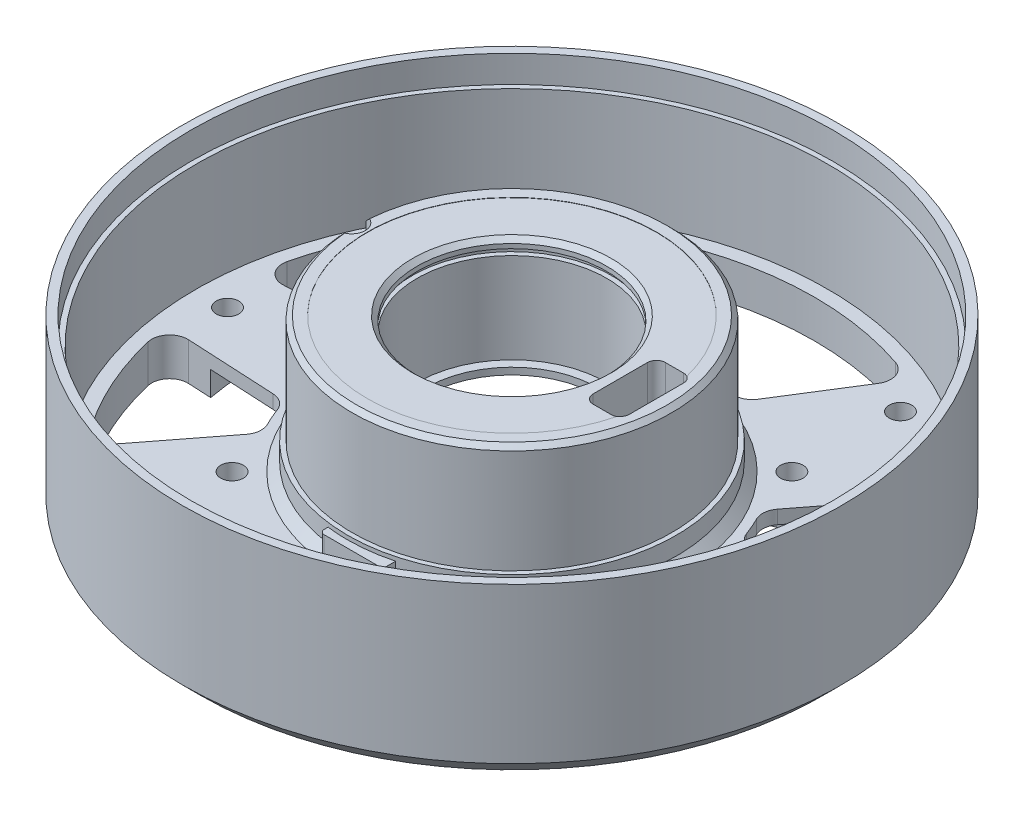
SolidWorks part; units mm, degrees
ref_plane "Front Plane" through (0, 0, 0) normal (0, 0, 1) x (1, 0, 0)
ref_plane "Top Plane" through (0, 0, 0) normal (0, 1, 0) x (1, 0, 0)
ref_plane "Right Plane" through (0, 0, 0) normal (1, 0, 0) x (0, 0, -1)
ref_axis "Axis1" through (0, 0, 0) along (0, 1, 0)
sketch "Sketch1" plane through (0, 0, 0) normal (0, 0, 1) x (1, 0, 0)
  line L0 (0, 0) -> (0, -50277.2651) construction
  line L1 (-17.7, 6) -> (-17.7, -6)
  line L2 (-17.7, -6) -> (-18.2, -6)
  line L3 (-18.2, -6) -> (-18.2, -8)
  line L4 (-19.2, -9) -> (-35, -9)
  line L7 (-35, -9) -> (-35, 3)
  line L8 (-35, 3) -> (-35.55, 3)
  line L9 (-35.55, 3) -> (-35.55, 6)
  line L10 (-35.55, 6) -> (-36.5, 6)
  line L11 (-36.5, 6) -> (-36.5, -11.2)
  line L12 (-34.5, -13.2) -> (-28.5, -13.2)
  line L13 (-28.5, -13.2) -> (-28.5, -10.5)
  line L14 (-28.5, -10.5) -> (-18.06, -10.5)
  line L23 (-16, 5.97) -> (-16, 6)
  line L24 (-16, 6) -> (-17.7, 6)
  line L25 (-19.25, -6) -> (19.25, -6) construction
  line L26 (19.25, 6) -> (-19.25, 6) construction
  line L27 (-34, 8) -> (-34, -6) construction
  line L31 (-16, 5.97) -> (-10.5, 5.97)
  line L32 (11.5, -13.2) -> (-11.5, -13.2) construction
  line L37 (-18.06, -10.5) -> (-14, -6.44)
  line L38 (-14, -6.44) -> (-9.5, -6.44)
  line L39 (-9.5, -6.44) -> (-9.5, -5.69)
  line L40 (-9.5, -5.69) -> (-10.5, -5.69)
  line L42 (-36.5, -11.2) -> (-34.5, -13.2)
  line L44 (-18.2, -8) -> (-19.2, -9)
  line L45 (-10.5, 5.97) -> (-10.5, 4.97)
  line L47 (-10.5, 4.97) -> (-11.03, 4.97)
  line L48 (-11.03, 4.97) -> (-11.03, 4.31)
  line L49 (-11.03, 4.31) -> (-10.5, 4.31)
  line L50 (-10.5, 4.31) -> (-10.5, -5.69)
  line L51 (8.9533, 4.31) -> (-8.9533, 4.31) construction
  line L52 (-8.9533, -5.69) -> (8.9533, -5.69) construction
  point P6 (-18.2, -9)
  point P15 (-36.5, -13.2)
  point P31 (-31.5, -13.2)
  dimension "D1" = 35.4
  dimension "D2" = 32
  dimension "D3" = 0.5
  dimension "D4" = 3
  dimension "D5" = 1
  dimension "D6" = 1.5
  dimension "D8" = 1.5
  dimension "D9" = 3
  dimension "D10" = 71.1
  dimension "D13" = 63
  dimension "D14" = 0.66
  dimension "D15" = 21
  dimension "D16" = 22.06
  dimension "D17" = 1
  dimension "D18" = 0.75
  dimension "D19" = 1
  dimension "D20" = 3.5
  dimension "D21" = 135
revolve "Revolve1" add sketch "Sketch1" angle 360 about L0
sketch "Sketch2" plane through (0, 0, 0) normal (0, 1, 0) x (1, 0, 0)
  circle A0 centre (-17.75, 0) radius 1.5
  dimension "D1" = 3
extrude "Cut-Extrude2" cut sketch "Sketch2" along normal up to next and the other way up to surface other way up to face at (0, -6, 18.2)
sketch "Sketch3" plane through (0, 0, 0) normal (0, 1, 0) x (1, 0, 0)
  circle A0 centre (-15.5, -15.5) radius 3.5
  circle A1 centre (15.5, -15.5) radius 3.5
  circle A2 centre (15.5, 15.5) radius 3.5
  circle A3 centre (-15.5, 15.5) radius 3.5
  dimension "D1" = 7
extrude "Boss-Extrude1" add sketch "Sketch3" against normal up to surface (1.5 mm away) from surface starting at face at (0, -10.5, 18.06)
hole_wizard "M3x0.5 Tapped Hole1" positions "Sketch4" profile "Sketch6" tap size "M3x0.5" standard "ANSI Metric" end condition through all
sketch "Sketch4" plane through (0, -12, 0) normal (0, -1, 0) x (-1, 0, 0)
  point P0 (-15.5, 15.5)
  point P3 (15.5, 15.5)
  point P6 (15.5, -15.5)
  point P9 (-15.5, -15.5)
sketch "Sketch6" plane through (15.5, -12, -15.5) normal (1, 0, 0) x (0, 0, -1)
  line L0 (0, 0) -> (0, 18)
  line L1 (0, 18) -> (1.25, 18)
  line L2 (1.25, 18) -> (1.25, 0.35)
  line L3 (1.25, 0.35) -> (1.6, 0)
  line L5 (1.6, 0) -> (0, 0)
  line L6 (-1.25, 0.35) -> (-1.6, 0) construction
  line L11 (0, -6.35) -> (0, 107.95) construction
  dimension "Thru Tap Drill Dia." = 2.5
  dimension "Thru Tap Drill Depth" = 18
  dimension "Near C'Sink Dia." = 3.2
  dimension "Near C'Sink Angle" = 90
cosmetic thread "Hole Thread5" parameters "D2"=3
cosmetic thread "Hole Thread6" parameters "D2"=3
cosmetic thread "Hole Thread7" parameters "D2"=3
cosmetic thread "Hole Thread8" parameters "D2"=3
sketch "Sketch7" plane through (0, 0, 0) normal (0, 1, 0) x (1, 0, 0)
  line L0 (-1.8, -12.5) -> (4.2, -18.5) construction
  line L1 (-1.8, -19) -> (4.2, -19)
  line L2 (-2.3, -18.5) -> (-2.3, -12.5)
  line L3 (-1.8, -12) -> (4.2, -12)
  line L4 (4.7, -18.5) -> (4.7, -12.5)
  arc A0 (4.2, -19) -> (4.7, -18.5) centre (4.2, -18.5) ccw
  arc A1 (-2.3, -12.5) -> (-1.8, -12) centre (-1.8, -12.5) cw
  arc A2 (4.2, -12) -> (4.7, -12.5) centre (4.2, -12.5) cw
  arc A3 (-1.8, -19) -> (-2.3, -18.5) centre (-1.8, -18.5) cw
  point P12 (1.2, -15.5)
  dimension "D1" = 0.5
  dimension "D2" = 15.5
  dimension "D3" = 1.2
  dimension "D4" = 7
  dimension "D5" = 7
extrude "Boss-Extrude2" add sketch "Sketch7" against normal offset from surface (4.06 mm away) 1.5 from surface starting at face at (0, -6.44, 9.5)
sketch "Sketch9" plane through (0, 0, 0) normal (0, 1, 0) x (1, 0, 0)
  circle A0 centre (0, 0) radius 23.35 construction
  circle A2 centre (0, -23.35) radius 5.15
  circle A5 centre (0, 23.35) radius 5.15
  circle A6 centre (0, 0) radius 28.5 construction
  circle A7 centre (0, 0) radius 18.2 construction
extrude "Cut-Extrude4" [suppressed] cut sketch "Sketch9" against normal through all
sketch "Sketch10" plane through (0, 0, 0) normal (0, 1, 0) x (1, 0, 0)
  line L1 (13, 4) -> (15, 4)
  line L2 (12, 3) -> (12, -3)
  line L3 (13, -4) -> (15, -4)
  line L4 (16, 3) -> (16, -3)
  line L5 (12, 4) -> (16, -4) construction
  line L6 (12, -4) -> (16, 4) construction
  arc A0 (15, -4) -> (16, -3) centre (15, -3) ccw
  arc A1 (15, 4) -> (16, 3) centre (15, 3) cw
  arc A2 (12, -3) -> (13, -4) centre (13, -3) ccw
  arc A3 (13, 4) -> (12, 3) centre (13, 3) ccw
  point P0 (14, 0)
  point P19 (10.5, 0)
  dimension "D1" = 1
  dimension "D2" = 1.5
  dimension "D3" = 4
  dimension "D4" = 8
extrude "Cut-Extrude5" cut sketch "Sketch10" against normal through all both and the other way through all
chamfer "Chamfer1" distance 0.5 angle 45 2 edges at (17.7, 6, 0) (0, 5.97, 10.5)
hole_wizard "M3x0.5 Tapped Hole2" positions "Sketch11" profile "Sketch12" tap size "M3x0.5" standard "ANSI Metric" end condition through all
sketch "Sketch11" plane through (0, -13.2, 0) normal (0, -1, 0) x (-1, 0, 0)
  circle A0 centre (0, 0) radius 31.5 construction
  point P0 (-31.5, 0)
  dimension "D2" = 63
sketch "Sketch12" plane through (31.5, -13.2, 0) normal (1, 0, 0) x (0, 0, -1)
  line L0 (0, 0) -> (0, 19.2)
  line L1 (0, 19.2) -> (1.25, 19.2)
  line L2 (1.25, 19.2) -> (1.25, 0.35)
  line L3 (1.25, 0.35) -> (1.6, 0)
  line L5 (1.6, 0) -> (0, 0)
  line L6 (-1.25, 0.35) -> (-1.6, 0) construction
  line L11 (0, -6.35) -> (0, 107.95) construction
  dimension "Thru Tap Drill Dia." = 2.5
  dimension "Thru Tap Drill Depth" = 19.2
  dimension "Near C'Sink Dia." = 3.2
  dimension "Near C'Sink Angle" = 90
cosmetic thread "Hole Thread12" parameters "D2"=3
pattern_circular "CirPattern2" count 6 over 360 about axis through (0, 0, 0) along (0, 1, 0) of "M3x0.5 Tapped Hole2"
sketch "Sketch13" plane through (0, 0, 0) normal (0, 1, 0) x (1, 0, 0)
  line L0 (0, 0) -> (-50000, 0) construction
  line L1 (0, 0) -> (0, 50000) construction
  line L4 (-11.82, 28.7635) -> (-6.6703, 20.5706)
  line L6 (11.82, 28.7635) -> (6.6703, 20.5706)
  line L7 (11.82, -28.7635) -> (6.6703, -20.5706)
  line L8 (-11.82, -28.7635) -> (-6.6703, -20.5706)
  line L17 (18.2922, 11.1143) -> (24.4053, 19.0243)
  line L18 (30.5528, 5.247) -> (20.6998, 5.7545)
  line L19 (30.5528, -5.247) -> (20.6998, -5.7545)
  line L20 (18.2922, -11.1143) -> (24.4053, -19.0243)
  line L21 (-18.2922, -11.1143) -> (-24.4053, -19.0243)
  line L22 (-30.5528, -5.247) -> (-20.6998, -5.7545)
  line L23 (-30.5528, 5.247) -> (-20.6998, 5.7545)
  line L24 (-18.2922, 11.1143) -> (-24.4053, 19.0243)
  arc A0 (-10.7696, 31.7217) -> (10.7696, 31.7217) centre (0, 0) cw
  arc A5 (-4.5286, 19.6858) -> (4.5286, 19.6858) centre (0, 0) cw
  arc A10 (4.6855, -18.6195) -> (2.7641, -19) centre (0, 0) ccw construction
  circle A16 centre (0, 0) radius 34.5 construction
  arc A17 (-4.5286, -19.6858) -> (4.5286, -19.6858) centre (0, 0) ccw
  arc A18 (-10.7696, -31.7217) -> (10.7696, -31.7217) centre (0, 0) ccw
  arc A27 (18.0842, 9.0002) -> (18.9285, 7.0535) centre (0, 0) cw
  arc A28 (27.6378, 18.9315) -> (32.6021, 7.7043) centre (0, 0) cw
  arc A29 (27.6378, -18.9315) -> (32.6021, -7.7043) centre (0, 0) ccw
  arc A30 (18.0842, -9.0002) -> (18.9285, -7.0535) centre (0, 0) ccw
  arc A31 (-18.0842, -9.0002) -> (-18.9285, -7.0535) centre (0, 0) cw
  arc A32 (-27.6378, -18.9315) -> (-32.6021, -7.7043) centre (0, 0) cw
  arc A33 (-27.6378, 18.9315) -> (-32.6021, 7.7043) centre (0, 0) ccw
  arc A34 (-18.0842, 9.0002) -> (-18.9285, 7.0535) centre (0, 0) ccw
  arc A35 (-18.9285, 7.0535) -> (-20.6998, 5.7545) centre (-20.8026, 7.7518) cw
  arc A36 (-18.0842, 9.0002) -> (-18.2922, 11.1143) centre (-19.8747, 9.8913) ccw
  arc A37 (-32.6021, 7.7043) -> (-30.5528, 5.247) centre (-30.6557, 7.2443) ccw
  arc A38 (-27.6378, 18.9315) -> (-24.4053, 19.0243) centre (-25.9878, 17.8013) cw
  arc A39 (-32.6021, -7.7043) -> (-30.5528, -5.247) centre (-30.6557, -7.2443) cw
  arc A40 (-27.6378, -18.9315) -> (-24.4053, -19.0243) centre (-25.9878, -17.8013) ccw
  arc A41 (-18.9285, -7.0535) -> (-20.6998, -5.7545) centre (-20.8026, -7.7518) ccw
  arc A42 (-18.0842, -9.0002) -> (-18.2922, -11.1143) centre (-19.8747, -9.8913) cw
  arc A43 (18.9285, -7.0535) -> (20.6998, -5.7545) centre (20.8026, -7.7518) cw
  arc A44 (18.0842, -9.0002) -> (18.2922, -11.1143) centre (19.8747, -9.8913) ccw
  arc A45 (32.6021, -7.7043) -> (30.5528, -5.247) centre (30.6557, -7.2443) ccw
  arc A46 (27.6378, -18.9315) -> (24.4053, -19.0243) centre (25.9878, -17.8013) cw
  arc A47 (32.6021, 7.7043) -> (30.5528, 5.247) centre (30.6557, 7.2443) cw
  arc A48 (27.6378, 18.9315) -> (24.4053, 19.0243) centre (25.9878, 17.8013) ccw
  arc A49 (10.7696, -31.7217) -> (11.82, -28.7635) centre (10.1267, -29.8278) ccw
  arc A50 (-10.7696, -31.7217) -> (-11.82, -28.7635) centre (-10.1267, -29.8278) cw
  arc A51 (4.5286, -19.6858) -> (6.6703, -20.5706) centre (4.977, -21.6349) cw
  arc A52 (-4.5286, -19.6858) -> (-6.6703, -20.5706) centre (-4.977, -21.6349) ccw
  arc A53 (18.9285, 7.0535) -> (20.6998, 5.7545) centre (20.8026, 7.7518) ccw
  arc A54 (4.5286, 19.6858) -> (6.6703, 20.5706) centre (4.977, 21.6349) ccw
  arc A55 (-4.5286, 19.6858) -> (-6.6703, 20.5706) centre (-4.977, 21.6349) cw
  arc A56 (10.7696, 31.7217) -> (11.82, 28.7635) centre (10.1267, 29.8278) cw
  arc A57 (18.0842, 9.0002) -> (18.2922, 11.1143) centre (19.8747, 9.8913) cw
  arc A58 (-10.7696, 31.7217) -> (-11.82, 28.7635) centre (-10.1267, 29.8278) ccw
  point P9 (0, 20.2)
  point P10 (0, 33.5)
  point P50 (-19.3421, 5.8244)
  point P53 (-17.5, 10.0892)
  point P56 (-33.1071, 5.1154)
  point P59 (-26.0146, 21.1066)
  point P62 (-33.1071, -5.1154)
  point P65 (-26.0146, -21.1066)
  point P68 (-19.3421, -5.8244)
  point P71 (-17.5, -10.0892)
  point P74 (19.3421, -5.8244)
  point P77 (17.5, -10.0892)
  point P80 (33.1071, -5.1154)
  point P83 (26.0146, -21.1066)
  point P86 (33.1071, 5.1154)
  point P89 (26.0146, 21.1066)
  point P92 (13.1161, -30.8256)
  point P95 (-13.1161, -30.8256)
  point P98 (5.8863, -19.3233)
  point P101 (-5.8863, -19.3233)
  point P104 (19.3421, 5.8244)
  point P107 (5.8863, 19.3233)
  point P110 (-5.8863, 19.3233)
  point P113 (13.1161, 30.8256)
  point P116 (17.5, 10.0892)
  point P119 (-13.1161, 30.8256)
  dimension "D1" = 1
  dimension "D2" = 1
  dimension "D3" = 2
extrude "Cut-Extrude6" cut sketch "Sketch13" against normal through all
